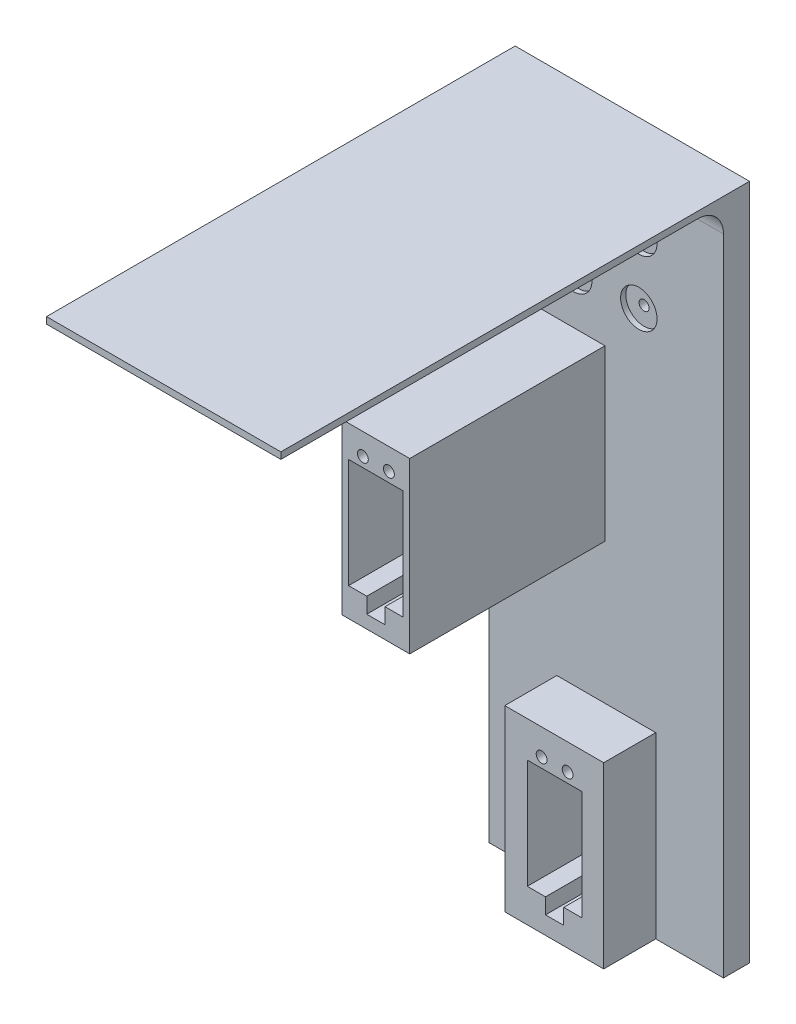
SolidWorks part; units mm, degrees
ref_plane "Front Plane" through (0, 0, 0) normal (0, 0, 1) x (1, 0, 0)
ref_plane "Top Plane" through (0, 0, 0) normal (0, 1, 0) x (1, 0, 0)
ref_plane "Right Plane" through (0, 0, 0) normal (1, 0, 0) x (0, 0, -1)
sketch "Sketch1" plane through (0, 0, 0) normal (0, 0, 1) x (1, 0, 0)
  line L1 (-75, 100) -> (75, 100)
  line L2 (-75, 100) -> (-75, -100)
  line L3 (-75, -100) -> (75, -100)
  line L4 (75, 100) -> (75, -100)
  line L5 (-75, 100) -> (75, -100) construction
  line L6 (-75, -100) -> (75, 100) construction
  point P0 (0, 0)
  dimension "D1" = 200
  dimension "D2" = 150
extrude "Boss-Extrude1" add sketch "Sketch1" along normal blind 30
sketch "Sketch2" plane through (0, 0, 30) normal (0, 0, 1) x (1, 0, 0)
  line L0 (75, -100) -> (75, 100) construction
  line L1 (-75, 100) -> (75, 100)
  line L2 (-75, 100) -> (-75, 95)
  line L3 (-75, 95) -> (75, 95)
  line L4 (75, 100) -> (75, 95)
  dimension "D1" = 5
extrude "Boss-Extrude2" add sketch "Sketch2" along normal blind 150
sketch "Sketch3" plane through (0, 0, 30) normal (0, 0, 1) x (1, 0, 0)
  line L0 (0, -100) -> (0, 0)
  line L1 (-75, -100) -> (75, -100) construction
  line L4 (0, 46.5) -> (0, 71.5)
  line L9 (-10.3251, 73.9819) -> (12.4051, 43.2014) construction
  line L10 (-12.4051, 43.2014) -> (10.3251, 73.9819) construction
  line L11 (-39.5, 13) -> (-39.5, 7)
  line L25 (-43, 13) -> (-36, 7) construction
  line L26 (-43, 7) -> (-36, 13) construction
  line L27 (-15.8, 46.5) -> (-12.5, 46.5)
  line L28 (-12.5, 46.5) -> (12.5, 46.5)
  line L29 (-12.5, 59) -> (12.5, 59)
  line L30 (12.5, 46.5) -> (-12.5, 46.5)
  line L31 (12.5, 46.5) -> (12.5, 71.5)
  line L32 (12.5, 71.5) -> (-12.5, 71.5)
  line L33 (-12.5, 46.5) -> (-12.5, 71.5)
  circle A0 centre (12.5, 46.5) radius 1.65
  circle A1 centre (-12.5, 46.5) radius 1.65
  circle A2 centre (12.5, 71.5) radius 1.65
  circle A3 centre (-12.5, 71.5) radius 1.65
  circle A4 centre (-12.5, 71.5) radius 3.3
  circle A5 centre (12.5, 71.5) radius 3.3
  circle A6 centre (12.5, 46.5) radius 3.3
  circle A7 centre (-12.5, 46.5) radius 3.3
  point P5 (0, 60)
  point P22 (-39.5, 10)
  dimension "D13" = 3.3
  dimension "D14" = 6.6
  dimension "D7" = 6
  dimension "D8" = 7
  dimension "D11" = 25
  dimension "D12" = 25
extrude "Cut-Extrude3" cut sketch "Sketch3" against normal blind 80 contours L11 | L11 | A1 L27 L33 | A1 L28 L27 | A1 L33 L28 | L31 A0 L30 | L30 A0 L31 | A2 L32 L31 | A2 L31 L32 | L32 A3 L33 | L33 A3 L32 region at (-12.5, 45.7997, 30) region at (-11.7997, 47.2003, 30) region at (11.7997, 47.2003, 30) region at (12.7334, 46.2666, 30) region at (-13.2003, 47.2003, 30) region at (-11.7997, 70.7997, 30) region at (-12.7334, 71.7334, 30) region at (12.7334, 71.7334, 30) region at (11.7997, 70.7997, 30)
ref_plane "Plane1" through (0, 0, 30) normal (0, 0, 1) x (1, 0, 0)
sketch "Sketch6" plane through (0, 0, 30) normal (0, 0, 1) x (1, 0, 0)
  circle A0 centre (-12.5, 71.5) radius 5
  circle A1 centre (12.5, 71.5) radius 5
  circle A2 centre (-12.5, 46.5) radius 5
  circle A3 centre (12.5, 46.5) radius 5
  dimension "D1" = 10
  dimension "D2" = 10
  dimension "D3" = 10
  dimension "D4" = 10
extrude "Cut-Extrude5" cut sketch "Sketch6" against normal blind 22
sketch "Sketch7" plane through (0, 0, 8) normal (0, 0, 1) x (1, 0, 0)
  circle A0 centre (-12.5, 71.5) radius 1.925
  circle A1 centre (12.5, 71.5) radius 1.925
  circle A2 centre (-12.5, 46.5) radius 1.925
  circle A3 centre (12.5, 46.5) radius 1.925
  dimension "D1" = 3.85
  dimension "D2" = 3.85
  dimension "D3" = 3.85
  dimension "D4" = 3.85
extrude "Cut-Extrude6" cut sketch "Sketch7" against normal blind 5
sketch "Sketch9" plane through (0, 0, 30) normal (0, 0, 1) x (1, 0, 0)
  line L0 (-12.5, 46.5) -> (12.5, 46.5)
  line L1 (12.5, 46.5) -> (0, 46.5)
  line L2 (0, 46.5) -> (1.1812, -69.9316)
  line L3 (1.1812, -69.9316) -> (1.1812, -115.5276)
  line L4 (-13.5, 15.5) -> (0.3145, 15.5)
  line L5 (-2.604, -89.8179) -> (4.396, -89.8179)
  line L6 (11.396, -83.8179) -> (11.396, -41.8179)
  line L7 (-2.604, -83.8179) -> (-9.604, -83.8179)
  line L8 (4.396, -89.8179) -> (4.396, -83.8179)
  line L9 (4.396, -83.8179) -> (11.396, -83.8179)
  line L10 (-9.604, -41.8179) -> (-9.604, -83.8179)
  line L11 (-24, 15.5) -> (-3, 15.5)
  line L12 (-17, -26.5) -> (-24, -26.5)
  line L18 (-24, 15.5) -> (-24, -26.5)
  line L19 (-10, -32.5) -> (-10, -26.5)
  line L20 (-17, -32.5) -> (-10, -32.5)
  line L21 (-17, -26.5) -> (-17, -32.5)
  line L22 (-10, -26.5) -> (-3, -26.5)
  line L23 (-3, -26.5) -> (-3, 15.5)
  line L24 (-9.604, -41.8179) -> (11.396, -41.8179)
  line L25 (-2.604, -83.8179) -> (-2.604, -89.8179)
  circle A6 centre (-8.5, 19.25) radius 2.08
  circle A7 centre (-18.5, 19.25) radius 2.08
  circle A8 centre (5.896, -38.0679) radius 2.08
  circle A9 centre (-4.104, -38.0679) radius 2.08
  point P16 (-39.5, 65.9329)
  dimension "D6" = 42
  dimension "D1" = 13.8145
fillet "Fillet1" radius 5 1 edges at (0, 95, 30)
extrude "Cut-Extrude7" cut sketch "Sketch9" against normal blind 30 contours L22 L23 L11 L18 L12 L21 L20 L19 | A7 | A6 region at (-13.5, -6.5909, 30) region at (-8.5, 19.25, 30) region at (-18.5, 19.25, 30)
sketch "Sketch10" plane through (0, 0, 30) normal (0, 0, 1) x (1, 0, 0)
  line L8 (0.1568, -105.1715) -> (0.1568, -105.1715)
  line L9 (8.2068, -105.9215) -> (-7.8932, -105.9215) construction
ref_plane "Plane2" through (0, 0, 0) normal (0, 0, -1) x (-1, 0, 0)
sketch "Sketch12" plane through (0, 0, 0) normal (0, 0, -1) x (-1, 0, 0)
  line L0 (13.5, 15.5) -> (13.5, -37.4614)
  line L1 (24, 15.5) -> (3, 15.5) construction
  line L2 (13.5, -37.4614) -> (26.5, -37.4614)
  line L3 (26.5, -37.4614) -> (26.5, 27.5386)
  line L4 (3, 15.5) -> (3, -26.5)
  line L5 (26.5, -37.4614) -> (0.5, -37.4614)
  line L6 (26.5, -37.4614) -> (26.5, 27.5386)
  line L7 (26.5, 27.5386) -> (0.5, 27.5386)
  line L8 (0.5, -37.4614) -> (0.5, 27.5386)
  line L9 (3, -26.5) -> (10, -26.5)
  line L10 (10, -26.5) -> (10, -32.5)
  line L11 (10, -32.5) -> (17, -32.5)
  line L12 (17, -32.5) -> (17, -26.5)
  line L13 (17, -26.5) -> (24, -26.5)
  line L14 (24, -26.5) -> (24, 15.5)
  line L15 (24, 15.5) -> (3, 15.5)
  circle A0 centre (8.5, 19.25) radius 2.08
  circle A1 centre (18.5, 19.25) radius 2.08
  dimension "D1" = 13
  dimension "D2" = 65
  dimension "D3" = 26
  dimension "D4" = 65
extrude "Boss-Extrude5" add sketch "Sketch12" against normal blind 85 contours L15 L14 L13 L12 L11 L2 L3 L7 L8 L5 L10 L9 L4 A1 A0 region at (-7, -36.7613, 0)
sketch "Sketch13" plane through (0, 0, 0) normal (0, 0, -1) x (-1, 0, 0)
  line L0 (-75, -100) -> (-75, -160)
  line L1 (-75, -160) -> (75, -160)
  line L2 (75, -160) -> (75, -100)
  line L3 (75, -100) -> (-75, -100) construction
  line L4 (75, -100) -> (-75, -100)
  dimension "D1" = 60
extrude "Boss-Extrude6" add sketch "Sketch13" against normal blind 30
sketch "Sketch15" plane through (0, 0, 30) normal (0, 0, 1) x (1, 0, 0)
  line L0 (-10.3432, -105.1715) -> (10.6568, -105.1715)
  line L1 (10.6568, -105.1715) -> (10.6568, -147.1715)
  line L2 (10.6568, -147.1715) -> (3.6568, -147.1715)
  line L3 (3.6568, -147.1715) -> (3.6568, -153.1715)
  line L4 (3.6568, -153.1715) -> (-3.3432, -153.1715)
  line L5 (-3.3432, -153.1715) -> (-3.3432, -147.1715)
  line L6 (-3.3432, -147.1715) -> (-10.3432, -147.1715)
  line L7 (-10.3432, -147.1715) -> (-10.3432, -105.1715)
  circle A0 centre (-4.8432, -101.4215) radius 2.08
  circle A1 centre (5.1568, -101.4215) radius 2.08
  dimension "D1" = 4.16
  dimension "D2" = 4.16
extrude "Cut-Extrude8" cut sketch "Sketch15" against normal blind 30
sketch "Sketch16" plane through (0, 0, 30) normal (0, 0, 1) x (1, 0, 0)
  circle A0 centre (-12.5, 71.5) radius 7
  circle A1 centre (12.5, 71.5) radius 7
  circle A2 centre (12.5, 46.5) radius 7
  circle A3 centre (-12.5, 46.5) radius 7
  dimension "D1" = 14
extrude "Cut-Extrude9" cut sketch "Sketch16" against normal blind 22
sketch "Sketch17" plane through (0, 0, 0) normal (0, 0, -1) x (-1, 0, 0)
  line L0 (-75, -160) -> (75, -160) construction
  line L1 (75, 100) -> (55, 100)
  line L2 (75, 100) -> (75, -160)
  line L3 (75, -160) -> (55, -160)
  line L4 (55, 100) -> (55, -160)
  line L5 (-55, -160) -> (-75, -160)
  line L6 (-75, 100) -> (-75, -160)
  line L7 (-55, 100) -> (-75, 100)
  line L8 (-55, 100) -> (-55, -160)
  dimension "D1" = 20
extrude "Cut-Extrude10" cut sketch "Sketch17" against normal blind 180
sketch "Sketch19" plane through (0, 0, 30) normal (0, 0, 1) x (1, 0, 0)
  line L0 (-55, 90) -> (55, 90)
  line L1 (55, 90) -> (55, -160)
  line L2 (55, -160) -> (19, -160)
  line L3 (55, -160) -> (-55, -160) construction
  line L4 (19, -160) -> (19, -91.3882)
  line L5 (19, -91.3882) -> (-19, -91.3882)
  line L6 (-19, -91.3882) -> (-19, -160)
  line L7 (-19, -160) -> (-55, -160)
  line L8 (-55, -160) -> (-55, 90)
  line L9 (-26.5, 27.5386) -> (-26.5, -37.4614)
  line L10 (-26.5, -37.4614) -> (-0.5, -37.4614) construction
  line L11 (-26.5, 27.5386) -> (-26.5, -37.4614) construction
  line L12 (-26.5, -37.4614) -> (-0.5, -37.4614)
  line L13 (-0.5, -37.4614) -> (-0.5, 27.5386)
  line L14 (-0.5, 27.5386) -> (-26.5, 27.5386)
  dimension "D1" = 36
  dimension "D2" = 36
extrude "Cut-Extrude11" cut sketch "Sketch19" against normal blind 20
sketch "Sketch20" plane through (0, 0, 10) normal (0, 0, 1) x (1, 0, 0)
  line L1 (-55, 90) -> (55, 90)
  line L2 (-55, 90) -> (-55, 97.4806)
  line L3 (-55, 97.4806) -> (55, 97.4806)
  line L4 (55, 90) -> (55, 97.4806)
extrude "Cut-Extrude12" cut sketch "Sketch20" along normal blind 200
fillet "Fillet2" radius 10 1 edges at (0, 97.4806, 10)
sketch "Sketch21" plane through (0, 0, 0) normal (0, 0, -1) x (-1, 0, 0)
  line L0 (-55, -160) -> (55, -160) construction
  line L1 (55, 100) -> (45, 100)
  line L2 (55, 100) -> (55, -160)
  line L3 (55, -160) -> (45, -160)
  line L4 (45, 100) -> (45, -160)
  line L5 (-45, -160) -> (-55, -160)
  line L6 (-45, 100) -> (-55, 100)
  line L7 (-45, 100) -> (-45, -160)
  line L8 (-55, 100) -> (-55, -160)
  dimension "D1" = 10
extrude "Cut-Extrude13" cut sketch "Sketch21" against normal blind 200
